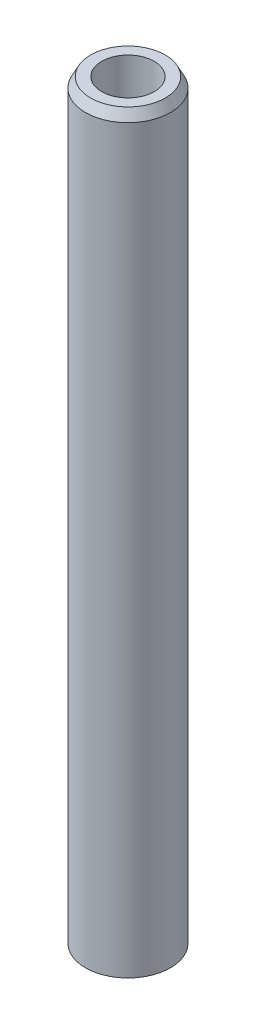
SolidWorks part; units mm, degrees
ref_plane "Front Plane" through (0, 0, 0) normal (0, 0, 1) x (1, 0, 0)
ref_plane "Top Plane" through (0, 0, 0) normal (0, 1, 0) x (1, 0, 0)
ref_plane "Right Plane" through (0, 0, 0) normal (1, 0, 0) x (0, 0, -1)
sketch "Sketch1" plane through (0, 0, 0) normal (0, 1, 0) x (1, 0, 0)
  circle A0 centre (0, 0) radius 10
  dimension "SHAFT_OD" = 20
extrude "Boss-Extrude1" add sketch "Sketch1" along normal blind 177.8742
sketch "Sketch2" plane through (0, 0, 0) normal (0, 1, 0) x (1, 0, 0)
  circle A0 centre (0, 0) radius 6.1865
  dimension "BORE_D" = 12.373
extrude "Cut-Extrude1" cut sketch "Sketch2" along normal through all
chamfer "Chamfer1" distance 2.3517 angle 27.329 2 edges at (0, 177.8742, 10) (0, 0, 10) first distance on face at (0, 177.8742, 10) first distance on face at (0, 0, 6.1865)
